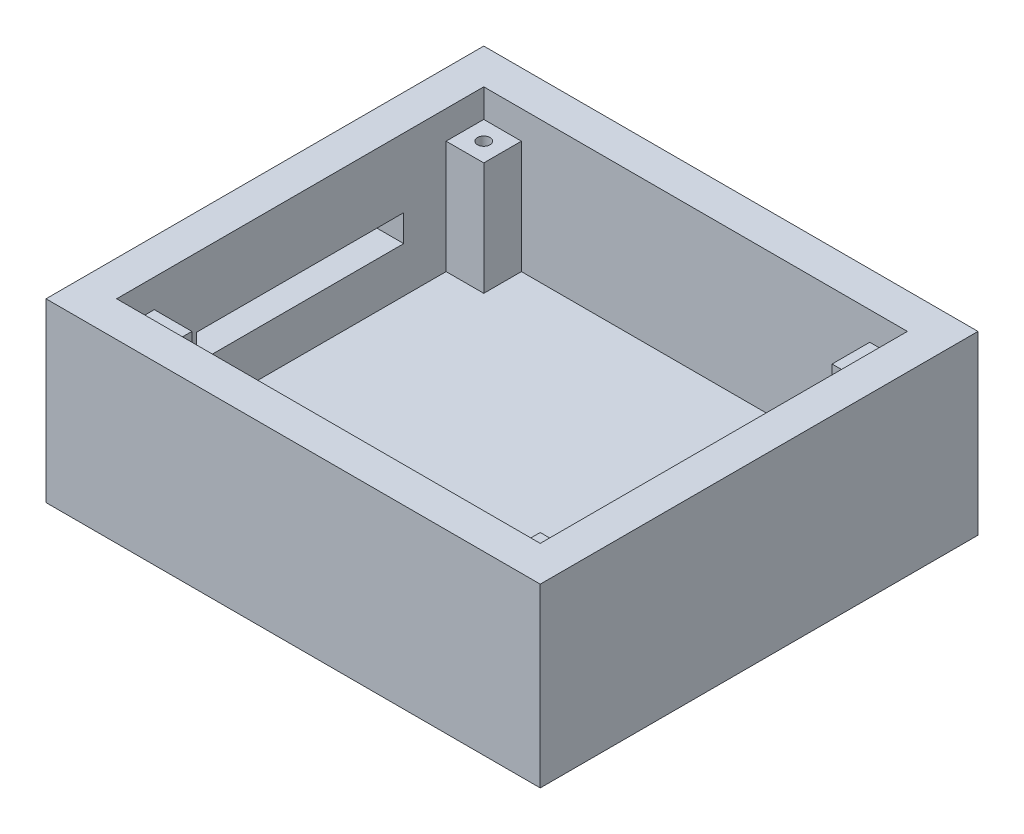
SolidWorks part; units mm, degrees
ref_plane "Front Plane" through (0, 0, 0) normal (0, 0, 1) x (1, 0, 0)
ref_plane "Top Plane" through (0, 0, 0) normal (0, 1, 0) x (1, 0, 0)
ref_plane "Right Plane" through (0, 0, 0) normal (1, 0, 0) x (0, 0, -1)
sketch "Sketch1" plane through (0, 0, 0) normal (0, 1, 0) x (1, 0, 0)
  line L0 (-57.15, 0) -> (-61.9125, 0) construction
  line L1 (-57.15, 49.53) -> (57.15, 49.53)
  line L2 (-57.15, 49.53) -> (-57.15, -49.53)
  line L3 (-57.15, -49.53) -> (57.15, -49.53)
  line L4 (57.15, 49.53) -> (57.15, -49.53)
  line L5 (-57.15, 49.53) -> (57.15, -49.53) construction
  line L6 (-57.15, -49.53) -> (57.15, 49.53) construction
  line L7 (57.15, 0) -> (61.9125, 0) construction
  line L8 (-66.675, 59.055) -> (-57.15, 59.055)
  line L9 (-66.675, 59.055) -> (-66.675, -59.055)
  line L10 (-66.675, -59.055) -> (-57.15, -59.055)
  line L11 (-57.15, 59.055) -> (-57.15, -59.055)
  line L12 (-66.675, 59.055) -> (-57.15, -59.055) construction
  line L13 (-66.675, -59.055) -> (-57.15, 59.055) construction
  line L14 (-57.15, 59.055) -> (57.15, 59.055)
  line L15 (66.675, 59.055) -> (57.15, 59.055)
  line L16 (66.675, 59.055) -> (66.675, -59.055)
  line L17 (66.675, -59.055) -> (57.15, -59.055)
  line L18 (57.15, 59.055) -> (57.15, -59.055)
  line L19 (66.675, 59.055) -> (57.15, -59.055) construction
  line L20 (66.675, -59.055) -> (57.15, 59.055) construction
  line L21 (-57.15, -59.055) -> (57.15, -59.055)
  point P0 (0, 0)
  dimension "D1" = 114.3
  dimension "D2" = 99.06
  dimension "D3" = 4.7625
  dimension "D4" = 118.11
  dimension "D5" = 4.7625
  dimension "D6" = 118.11
extrude "Boss-Extrude1" add sketch "Sketch1" along normal blind 9.525 contours L4 L1 L2 L3 region at (0, 0, 0)
extrude "Boss-Extrude2" add sketch "Sketch1<3>" along normal blind 47.625 contours L11 L8 L9 L10 L2 | L18 L14 L11 L1 | L15 L18 L4 L17 L16 | L11 L21 L18 L3 region at (0, 0, -54.2925) region at (-61.9125, 0, 0) region at (61.9125, 0, 0) region at (0, 0, 54.2925)
sketch "Sketch1<3>" plane through (0, 0, 0) normal (0, 1, 0) x (1, 0, 0) same geometry as "Sketch1"
sketch "Sketch3" plane through (0, 9.525, 0) normal (0, 1, 0) x (1, 0, 0)
  line L0 (-46.99, 44.45) -> (-57.15, 44.45) construction
  line L1 (-57.15, 49.53) -> (-46.99, 49.53)
  line L2 (-57.15, 49.53) -> (-57.15, 39.37)
  line L3 (-57.15, 39.37) -> (-46.99, 39.37)
  line L4 (-46.99, 49.53) -> (-46.99, 39.37)
  line L5 (57.15, 49.53) -> (46.99, 49.53)
  line L6 (57.15, 49.53) -> (57.15, 39.37)
  line L7 (57.15, 39.37) -> (46.99, 39.37)
  line L8 (46.99, 49.53) -> (46.99, 39.37)
  line L9 (57.15, -49.53) -> (46.99, -49.53)
  line L10 (57.15, -49.53) -> (57.15, -39.37)
  line L11 (57.15, -39.37) -> (46.99, -39.37)
  line L12 (46.99, -49.53) -> (46.99, -39.37)
  line L13 (-57.15, -49.53) -> (-46.99, -49.53)
  line L14 (-57.15, -49.53) -> (-57.15, -39.37)
  line L15 (-57.15, -39.37) -> (-46.99, -39.37)
  line L16 (-46.99, -49.53) -> (-46.99, -39.37)
  line L17 (46.99, 44.45) -> (57.15, 44.45) construction
  line L18 (-46.99, -44.45) -> (-57.15, -44.45) construction
  line L19 (46.99, -44.45) -> (57.15, -44.45) construction
  circle A0 centre (-52.07, 44.45) radius 1.7018
  circle A1 centre (52.07, 44.45) radius 1.7018
  circle A2 centre (52.07, -44.45) radius 1.7018
  circle A3 centre (-52.07, -44.45) radius 1.7018
  dimension "D1" = 10.16
  dimension "D2" = 10.16
  dimension "D3" = 10.16
  dimension "D4" = 10.16
  dimension "D5" = 10.16
  dimension "D6" = 10.16
  dimension "D7" = 10.16
  dimension "D8" = 10.16
extrude "Boss-Extrude3" add sketch "Sketch3" along normal blind 30.48
sketch "Sketch5" plane through (-66.675, 0, 0) normal (-1, 0, 0) x (0, 0, 1)
  line L0 (-59.055, 0) -> (-59.055, 25.4) construction
  line L1 (-59.055, 47.625) -> (-59.055, 0) construction
  line L2 (-59.055, 25.4) -> (59.055, 25.4) construction
  line L3 (59.055, 47.625) -> (59.055, 0) construction
  line L5 (-27.94, 29.0195) -> (27.94, 29.0195)
  line L6 (-27.94, 29.0195) -> (-27.94, 21.7805)
  line L7 (-27.94, 21.7805) -> (27.94, 21.7805)
  line L8 (27.94, 29.0195) -> (27.94, 21.7805)
  line L9 (-27.94, 29.0195) -> (27.94, 21.7805) construction
  line L10 (-27.94, 21.7805) -> (27.94, 29.0195) construction
  point P5 (0, 25.4)
  dimension "D1" = 25.4
  dimension "D2" = 55.88
  dimension "D3" = 7.239
extrude "Cut-Extrude1" cut sketch "Sketch5" against normal blind 30.48
